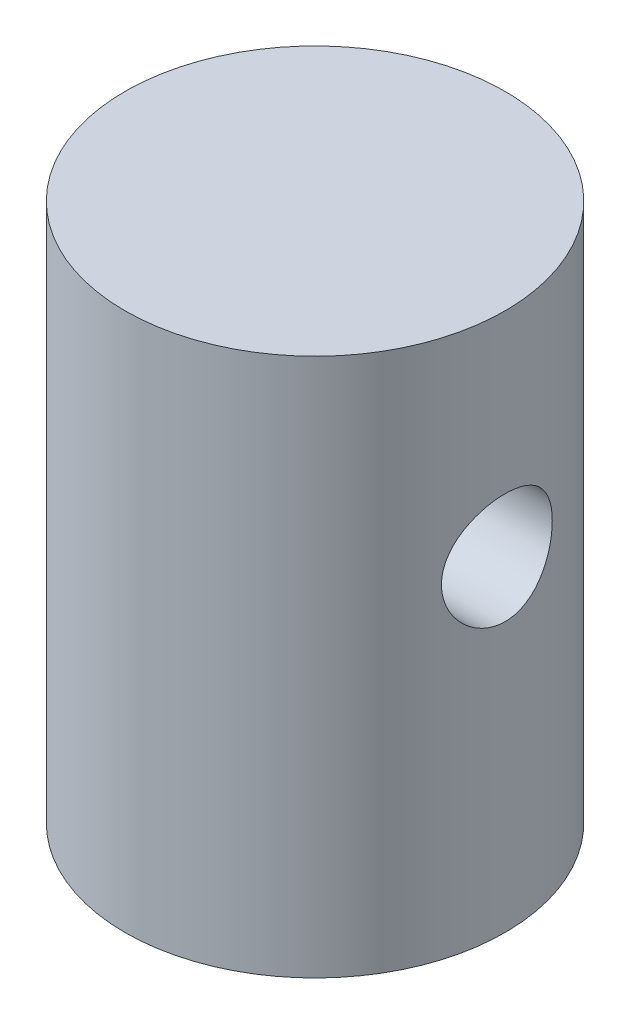
SolidWorks part; units mm, degrees
material "ASTM A36 Steel"
ref_plane "Front Plane" through (0, 0, 0) normal (0, 0, 1) x (1, 0, 0)
ref_plane "Top Plane" through (0, 0, 0) normal (0, 1, 0) x (1, 0, 0)
ref_plane "Right Plane" through (0, 0, 0) normal (1, 0, 0) x (0, 0, -1)
sketch "Sketch1" plane through (0, 0, 0) normal (0, 1, 0) x (1, 0, 0)
  circle A0 centre (0, 0) radius 6
extrude "Boss-Extrude1" add sketch "Sketch1" along normal blind 17
sketch "Sketch2" plane through (0, 0, 0) normal (1, 0, 0) x (0, 0, -1)
  circle A0 centre (0, 10.25) radius 1.75
extrude "Cut-Extrude1" cut sketch "Sketch2" against normal blind 17 and the other way blind 17
